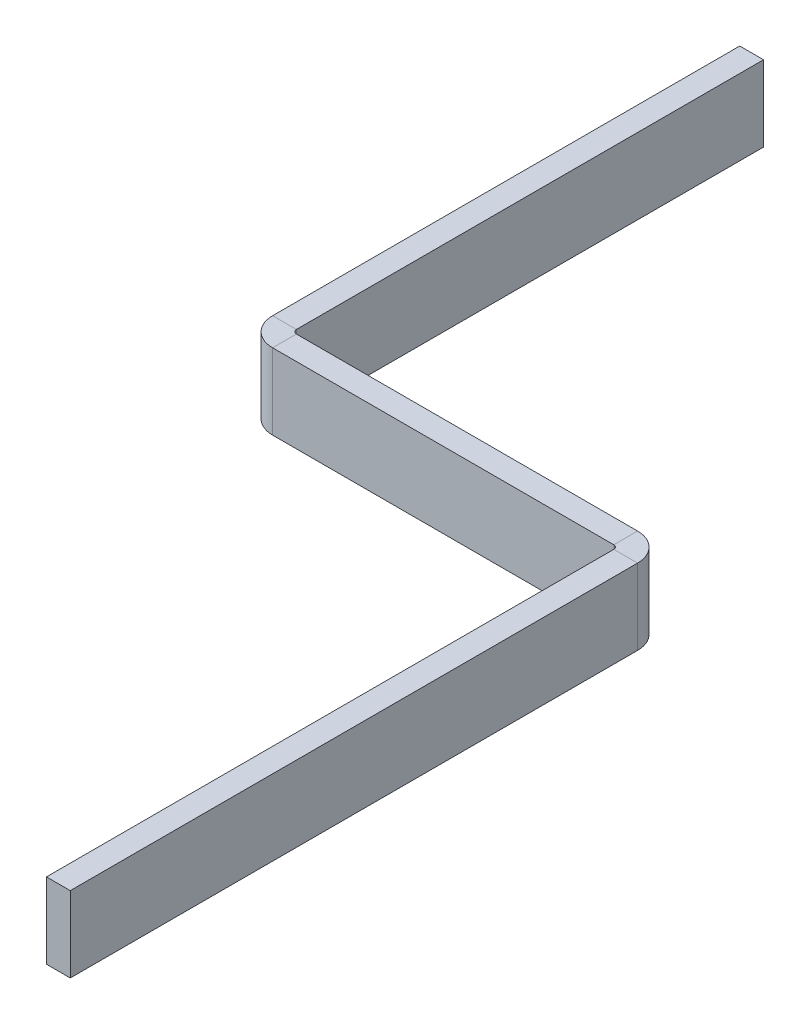
SolidWorks part; units mm, degrees
note: The reader was unsure of these and kept them because the rebuilt part matched: flange length of "Edge-Flange1", "Edge-Flange2".
ref_plane "Front Plane" through (0, 0, 0) normal (0, 0, 1) x (1, 0, 0)
ref_plane "Top Plane" through (0, 0, 0) normal (0, 1, 0) x (1, 0, 0)
ref_plane "Right Plane" through (0, 0, 0) normal (1, 0, 0) x (0, 0, -1)
sketch "Sketch1" plane through (0, 0, 0) normal (1, 0, 0) x (0, 0, -1)
  line L1 (-62.3752, -9.5351) -> (62.3752, -9.5351)
  line L2 (-62.3752, -9.5351) -> (-62.3752, 9.5351)
  line L3 (-62.3752, 9.5351) -> (62.3752, 9.5351)
  line L4 (62.3752, -9.5351) -> (62.3752, 9.5351)
  line L5 (-62.3752, -9.5351) -> (62.3752, 9.5351) construction
  line L6 (-62.3752, 9.5351) -> (62.3752, -9.5351) construction
  point P0 (0, 0)
base flange "Base-Flange1" sketch "Sketch1" thickness 6 reverse thickness direction no parameters "D1"=1
ref_plane "Plane1" through (0, 9.5351, 62.3752) normal (0, -1, 0) x (-1, 0, 0)
edge flange "Edge-Flange1" sketch "Sketch9" flange angle 90 flange length 100 flange position material inside bend radius 1 thickness 6 relief rectangular parameters "D6"=0
sketch "Sketch9" plane through (0, 0, 62.3752) normal (0, 0, 1) x (0, -1, 0)
  line L2 (-9.5351, 0) -> (-9.5351, 94)
  line L3 (-9.5351, 94) -> (9.5351, 94)
  line L4 (9.5351, 94) -> (9.5351, 0)
  line L7 (-9.5351, 0) -> (9.5351, 0) construction
  line L8 (-9.5351, 0) -> (9.5351, 0)
bend "EdgeBend1" bend radius 1 bend angle 90 parameters "D5"=1
edge flange "Edge-Flange2" sketch "Sketch12" flange angle 90 flange length 150 flange position material inside bend radius 1 thickness 6 relief rectangular parameters "D6"=0
sketch "Sketch12" plane through (94, 0, 62.3752) normal (1, 0, 0) x (0, 1, 0)
  line L0 (-9.5351, 0) -> (9.5351, 0) construction
  line L1 (-9.5351, 0) -> (9.5351, 0)
  line L2 (-9.5351, 0) -> (-9.5351, 144)
  line L3 (-9.5351, 144) -> (9.5351, 144)
  line L4 (9.5351, 144) -> (9.5351, 0)
bend "EdgeBend2" bend radius 1 bend angle 90 parameters "D5"=2
sketch "Bend-Lines1" [suppressed] plane through (0, 0, 0) normal (0, 1, 0) x (1, 0, 0)
sketch "Bounding-Box1" [suppressed] plane through (0, 0, 0) normal (0, 1, 0) x (1, 0, 0)
sheet metal parameters "Sheet-Metal1" thickness 6 parameters "D1"=1
flat pattern "Flat-Pattern1" [suppressed]
sketch "Bend-Lines2" plane through (0, 0, 0) normal (0, 1, 0) x (1, 0, 0)
sketch3d "Bounding-Box2" [suppressed]
  line L0 (-62.3752, -9.5351, 0) -> (62.3752, -9.5351, 0) construction
  line L1 (-62.3752, 9.5351, 0) -> (62.3752, 9.5351, 0) construction
  line L2 (-62.3752, -9.5351, 0) -> (-62.3752, 9.5351, 0) construction
  line L3 (62.3752, -9.5351, 0) -> (62.3752, 9.5351, 0) construction
sheet metal parameters "Sheet-Metal2" thickness 6 parameters "D1"=1
flat pattern "Flat-Pattern1"
sketch "Bend-Lines2" plane through (0, 0, 0) normal (1, 0, 0) x (0, 0, -1)
  line L0 (-58.5168, 9.5351) -> (-58.5168, -9.5351) construction
  line L1 (-58.5168, 9.5351) -> (-58.5168, -9.5351) construction
sketch3d "Bounding-Box2" [suppressed]
  line L0 (62.3752, -9.5351, 0) -> (-154.6584, -9.5351, 0) construction
  line L1 (62.3752, 9.5351, 0) -> (-154.6584, 9.5351, 0) construction
  line L2 (62.3752, -9.5351, 0) -> (62.3752, 9.5351, 0) construction
  line L3 (-154.6584, -9.5351, 0) -> (-154.6584, 9.5351, 0) construction
bend of the flat pattern "Flatten-<EdgeBend1>1"
sheet metal parameters "Sheet-Metal3" thickness 6 parameters "D1"=1
flat pattern "Flat-Pattern1"
sketch "Bend-Lines2" plane through (0, 0, 0) normal (1, 0, 0) x (0, 0, -1)
  line L0 (-58.5168, 9.5351) -> (-58.5168, -9.5351) construction
  line L1 (-58.5168, 9.5351) -> (-58.5168, -9.5351) construction
  line L2 (-150.8, 9.5351) -> (-150.8, -9.5351) construction
  line L3 (-150.8, 9.5351) -> (-150.8, -9.5351) construction
sketch3d "Bounding-Box2" [suppressed]
  line L0 (62.3752, -9.5351, 0) -> (-296.9415, -9.5351, 0) construction
  line L1 (62.3752, 9.5351, 0) -> (-296.9415, 9.5351, 0) construction
  line L2 (62.3752, -9.5351, 0) -> (62.3752, 9.5351, 0) construction
  line L3 (-296.9415, -9.5351, 0) -> (-296.9415, 9.5351, 0) construction
bend of the flat pattern "Flatten-<EdgeBend1>1"
bend of the flat pattern "Flatten-<EdgeBend2>1"
